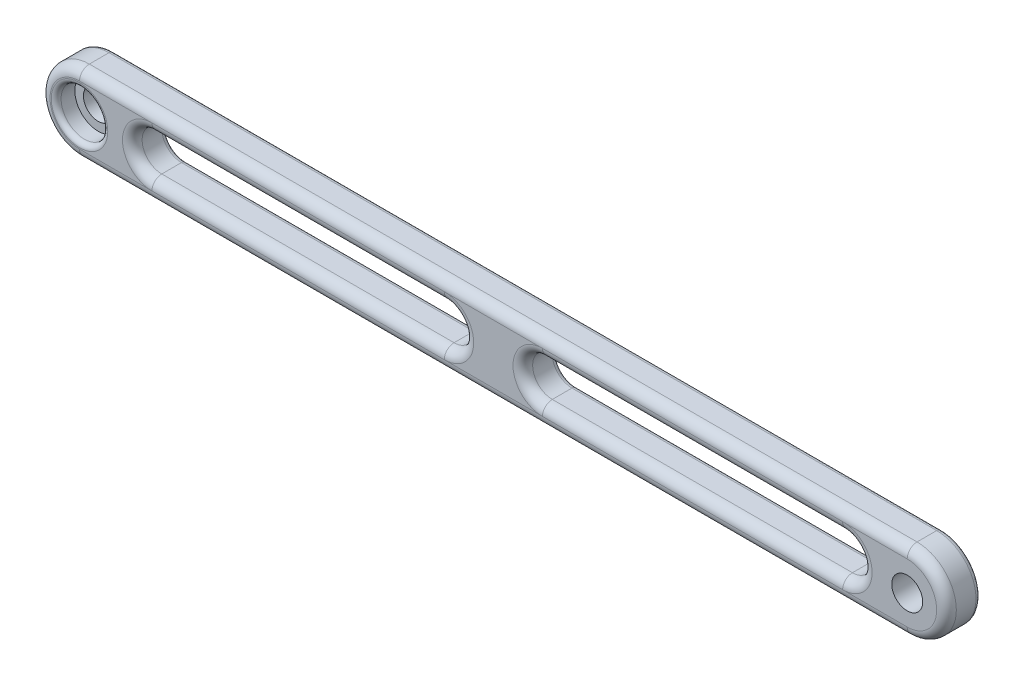
SolidWorks part; units mm, degrees
ref_plane "Front Plane" through (0, 0, 0) normal (0, 0, 1) x (1, 0, 0)
ref_plane "Top Plane" through (0, 0, 0) normal (0, 1, 0) x (1, 0, 0)
ref_plane "Right Plane" through (0, 0, 0) normal (1, 0, 0) x (0, 0, -1)
sketch "Sketch1" plane through (0, 0, 0) normal (0, 0, 1) x (1, 0, 0)
  line L0 (84.25, 0) -> (-84.25, 0) construction
  line L1 (-84.25, -8) -> (84.25, -8)
  line L3 (-84.25, 8) -> (84.25, 8)
  line L5 (-69.5, 4) -> (-10, 4)
  line L6 (-69.5, -4) -> (-10, -4)
  line L7 (10, 4) -> (71.1, 4)
  line L8 (10, -4) -> (71.1, -4)
  circle A0 centre (84.25, 0) radius 3.15
  circle A1 centre (84.25, 0) radius 3 construction
  arc A2 (84.25, -8) -> (84.25, 8) centre (84.25, 0) ccw
  circle A3 centre (-84.25, 0) radius 3
  arc A4 (-84.25, 8) -> (-84.25, -8) centre (-84.25, 0) ccw
  circle A5 centre (-84.25, 0) radius 4.75
  arc A6 (-69.5, 4) -> (-69.5, -4) centre (-69.5, 0) ccw
  arc A7 (-10, -4) -> (-10, 4) centre (-10, 0) ccw
  arc A8 (10, 4) -> (10, -4) centre (10, 0) ccw
  arc A9 (71.1, -4) -> (71.1, 4) centre (71.1, 0) ccw
  point P0 (0, 0)
  point P15 (0, 0)
  dimension "D2" = 6.3
  dimension "D3" = 6
  dimension "D4" = 8
  dimension "D1" = 6
  dimension "D6" = 9.5
  dimension "D7" = 6
  dimension "D8" = 6
  dimension "D10" = 6
  dimension "D11" = 6
  dimension "D5" = 168.5
  dimension "D9" = 4
extrude "Boss-Extrude1" add sketch "Sketch1" along normal mid plane 7 contours L3 A4 L1 A2 A5 A0 | A5 A3 region at (1.3907, 0, 0) region at (-88.8656, 0, 0)
extrude "Cut-Extrude1" cut sketch "Sketch1<3>" against normal offset from surface (3.8 mm away) 3.2 from surface contours A5 A3 region at (-88.8656, 0, 0) up to face at (40.55, 0, -3.5) starting at face at (40.55, 0, 3.5)
sketch "Sketch1<3>" plane through (0, 0, 0) normal (0, 0, 1) x (1, 0, 0) same geometry as "Sketch1"
fillet "Fillet1" radius 2 12 edges at (40.55, 4, 3.5) (75.1, 0, 3.5) (40.55, -4, 3.5) (-39.75, 4, 3.5) (-6, 0, 3.5) (-39.75, -4, 3.5) (-92.25, 0, 3.5) (0, 8, 3.5) (92.25, 0, 3.5) (6, 0, 3.5) (-73.5, 0, 3.5) (0, -8, 3.5)
fillet "Fillet2" radius 1 1 edges at (-79.5, 0, 3.5)
fillet "Fillet3" radius 1 12 edges at (6, 0, -3.5) (40.55, 4, -3.5) (75.1, 0, -3.5) (-39.75, 4, -3.5) (-6, 0, -3.5) (-39.75, -4, -3.5) (-92.25, 0, -3.5) (0, 8, -3.5) (92.25, 0, -3.5) (40.55, -4, -3.5) (-73.5, 0, -3.5) (0, -8, -3.5)
fillet "Fillet4" radius 0.2 2 edges at (87.4, 0, -3.5) (-81.25, 0, -3.5)
